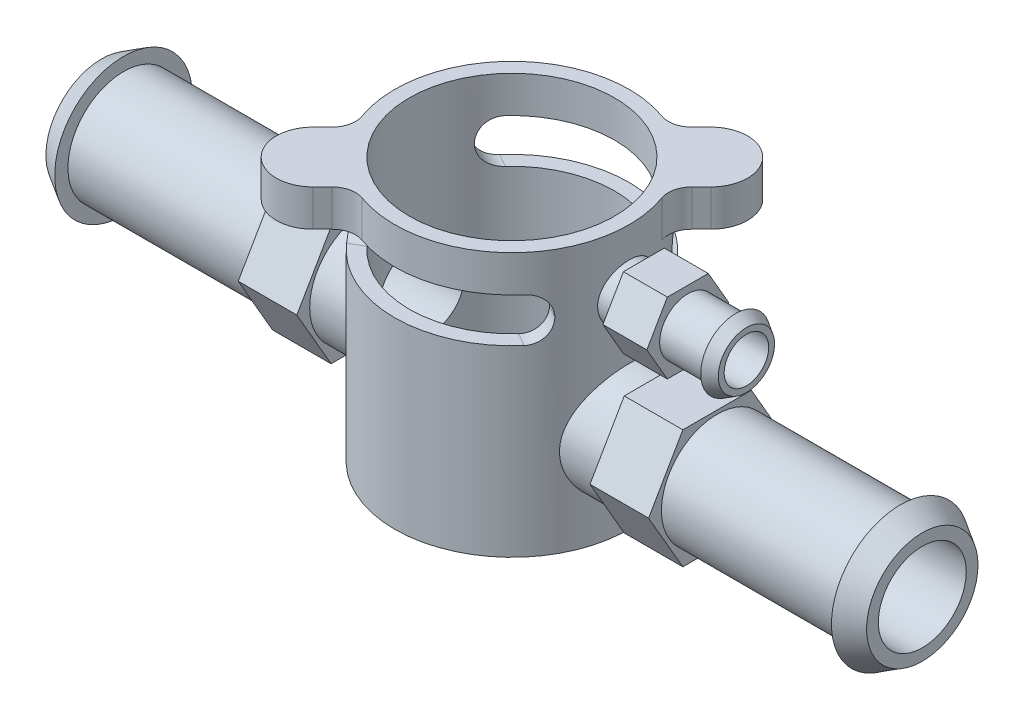
SolidWorks part; units mm, degrees
material "Chrome Stainless Steel"
ref_plane "Front Plane" through (0, 0, 0) normal (0, 0, 1) x (1, 0, 0)
ref_plane "Top Plane" through (0, 0, 0) normal (0, 1, 0) x (1, 0, 0)
ref_plane "Right Plane" through (0, 0, 0) normal (1, 0, 0) x (0, 0, -1)
ref_plane "Plane1" through (0, 0, 0) normal (-0.7071, 0, 0.7071) x (0.7071, 0, 0.7071)
sketch "Sketch1" plane through (0, 0, 0) normal (0, 1, 0) x (1, 0, 0)
  circle A0 centre (0, 0) radius 25.4
  dimension "D1" = 50.8
extrude "Boss-Extrude1" add sketch "Sketch1" along normal blind 57.15
sketch "Sketch2" plane through (0, 0, 0) normal (1, 0, 0) x (0, 0, -1)
  line L0 (0, 0) -> (0, 58.6228) construction
  line L2 (-7.424, 31.9088) -> (-14.848, 19.05)
  line L3 (-14.848, 19.05) -> (-7.424, 6.1912)
  line L4 (-7.424, 6.1912) -> (7.424, 6.1912)
  line L5 (7.424, 6.1912) -> (14.848, 19.05)
  line L6 (14.848, 19.05) -> (7.424, 31.9088)
  line L7 (7.424, 31.9088) -> (-7.424, 31.9088)
  line L8 (4.4361, 52.1335) -> (-4.4361, 52.1335)
  line L9 (-4.4361, 52.1335) -> (-8.8721, 44.45)
  line L10 (-8.8721, 44.45) -> (-4.4361, 36.7665)
  line L11 (-4.4361, 36.7665) -> (4.4361, 36.7665)
  line L12 (4.4361, 36.7665) -> (8.8721, 44.45)
  line L13 (8.8721, 44.45) -> (4.4361, 52.1335)
  circle A0 centre (0, 19.05) radius 9.525
  circle A1 centre (0, 44.45) radius 4.826
  circle A2 centre (0, 19.05) radius 12.065
  circle A3 centre (0, 44.45) radius 6.096
  circle A4 centre (0, 19.05) radius 12.8588 construction
  circle A5 centre (0, 44.45) radius 7.6835 construction
  dimension "D1" = 19.05
  dimension "D3" = 9.652
  dimension "D7" = 0.7937
  dimension "D8" = 1.5875
  dimension "D4" = 25.4
  dimension "D5" = 19.05
  dimension "D2" = 2.54
  dimension "D6" = 1.27
extrude "Boss-Extrude2" add sketch "Sketch2" along normal blind 88.9 contours A2
extrude "Boss-Extrude3" add sketch "Sketch2<3>" along normal blind 50.8 contours A3
sketch "Sketch2<3>" plane through (0, 0, 0) normal (1, 0, 0) x (0, 0, -1) same geometry as "Sketch2"
sketch "Sketch3" plane through (0, 0, 0) normal (0, 0, 1) x (1, 0, 0)
  line L0 (88.9, 31.115) -> (84.1375, 33.9725)
  line L1 (84.1375, 33.9725) -> (84.1375, 31.115)
  line L2 (88.9, 31.115) -> (25.4, 31.115) construction
  line L3 (84.1375, 31.115) -> (88.9, 31.115)
  dimension "D1" = 4.7625
  dimension "D2" = 2.8575
revolve "Revolve1" add sketch "Sketch3" angle 360 about axis through (88.9, 19.05, 0) along (-1, 0, 0)
sketch "Sketch4" plane through (0, 0, 0) normal (0, 0, 1) x (1, 0, 0)
  line L0 (50.8, 50.546) -> (48.4187, 50.546)
  line L1 (50.8, 50.546) -> (25.4, 50.546) construction
  line L2 (48.4187, 50.546) -> (48.4187, 51.9748)
  line L3 (48.4187, 51.9748) -> (50.8, 50.546)
  dimension "D1" = 2.3813
  dimension "D2" = 1.4287
revolve "Revolve2" add sketch "Sketch4" angle 360 about axis through (50.8, 44.45, 0) along (-1, 0, 0)
extrude "Boss-Extrude5" add sketch "Sketch2<13>" along normal blind 12.7 from offset 31.75 contours L7 L2 L3 L4 L5 L6
sketch "Sketch2<13>" plane through (0, 0, 0) normal (1, 0, 0) x (0, 0, -1) same geometry as "Sketch2"
extrude "Boss-Extrude6" add sketch "Sketch2<14>" along normal blind 9.525 from offset 28.575 contours L9 L10 L11 L12 L13 L8
sketch "Sketch2<14>" plane through (0, 0, 0) normal (1, 0, 0) x (0, 0, -1) same geometry as "Sketch2"
mirror "Mirror2" about plane through (0, 0, 0) normal (1, 0, 0) of "Revolve1", "Boss-Extrude5", "Boss-Extrude2"
sketch "Sketch8" plane through (0, 57.15, 0) normal (0, 1, 0) x (1, 0, 0)
  circle A0 centre (0, 0) radius 25.4 construction
  circle A1 centre (0, 0) radius 25.4 construction
  circle A2 centre (0, 0) radius 22.225
  dimension "D1" = 3.175
extrude "Cut-Extrude2" cut sketch "Sketch8" against normal offset from surface (53.975 mm away) 3.175 up to face at (0, 0, 25.4)
ref_plane "Plane2" through (0, 0, 0) normal (-0.5, 0, 0.866) x (0, -1, 0)
ref_plane "Plane3" through (0, 44.45, 0) normal (0, 1, 0) x (1, 0, 0)
sketch "Sketch7" plane through (0, 44.45, 0) normal (0, 1, 0) x (1, 0, 0)
  line L0 (19.2474, 11.1125) -> (21.997, 12.7)
  line L1 (0, 0) -> (25.4, 0) construction
  line L2 (19.2474, -11.1125) -> (21.997, -12.7)
  line L3 (-19.2474, -11.1125) -> (-21.997, -12.7)
  line L4 (-19.2474, 11.1125) -> (-21.997, 12.7)
  line L5 (0, 0) -> (19.2474, -11.1125) construction
  line L6 (0, 0) -> (-19.2474, -11.1125) construction
  line L7 (0, 0) -> (-19.2474, 11.1125) construction
  line L8 (0, 0) -> (19.2474, 11.1125) construction
  circle A0 centre (0, 0) radius 25.4 construction
  arc A1 (21.997, 12.7) -> (-21.997, 12.7) centre (0, 0) ccw
  arc A2 (21.997, -12.7) -> (25.4, 0) centre (0, 0) ccw construction
  arc A3 (25.4, 0) -> (21.997, 12.7) centre (0, 0) ccw construction
  arc A4 (-21.997, 12.7) -> (-21.997, -12.7) centre (0, 0) ccw construction
  arc A5 (-21.997, -12.7) -> (21.997, -12.7) centre (0, 0) ccw
  arc A7 (-19.2474, -11.1125) -> (19.2474, -11.1125) centre (0, 0) ccw
  arc A8 (-19.2474, 11.1125) -> (-19.2474, -11.1125) centre (0, 0) ccw construction
  arc A9 (19.2474, -11.1125) -> (22.225, 0) centre (0, 0) ccw construction
  arc A10 (19.2474, 11.1125) -> (-19.2474, 11.1125) centre (0, 0) ccw
  arc A11 (22.225, 0) -> (19.2474, 11.1125) centre (0, 0) ccw construction
  circle A12 centre (0, 0) radius 22.225 construction
  dimension "D2" = 22.225
  dimension "D1" = 30
extrude "Cut-Extrude1" cut sketch "Sketch7" against normal mid plane 9.525
fillet "Fillet2" radius 4.7625 8 edges at (20.6222, 49.2125, -11.9063) (20.6222, 39.6875, -11.9063) (-20.6222, 49.2125, -11.9063) (-20.6222, 39.6875, -11.9063) (-20.6222, 49.2125, 11.9063) (-20.6222, 39.6875, 11.9063) (20.6222, 49.2125, 11.9063) (20.6222, 39.6875, 11.9063)
sketch "Sketch5" plane through (0, 57.15, 0) normal (0, 1, 0) x (1, 0, 0)
  line L0 (-21.5526, -21.5526) -> (21.5526, 21.5526) construction
  line L2 (-35.5409, 0) -> (35.5409, 0) construction
  line L3 (11.4483, 22.6737) -> (15.94, 27.1653)
  line L4 (15.94, 27.1653) -> (27.1653, 15.94) construction
  line L5 (27.1653, 15.94) -> (22.6737, 11.4483)
  circle A0 centre (0, 0) radius 25.4 construction
  arc A1 (15.94, 27.1653) -> (27.1653, 15.94) centre (21.5526, 21.5526) cw
  arc A2 (22.6737, 11.4483) -> (11.4483, 22.6737) centre (0, 0) ccw
  point P0 (0, 0)
  point P6 (0, 0)
  dimension "D1" = 45
  dimension "D3" = 15.875
  dimension "D2" = 30.48
extrude "Boss-Extrude4" add sketch "Sketch5" against normal up to surface (7.9375 mm away) contours A1 L5 A2 L3 up to face at (0, 49.2125, -19.8008)
fillet "Fillet1" radius 5.08 2 edges at (11.4483, 53.1812, -22.6737) (22.6737, 53.1812, -11.4483)
mirror "Mirror1" about plane through (0, 0, 0) normal (-0.7071, 0, 0.7071) of "Fillet1", "Boss-Extrude4"
extrude "Cut-Extrude3" cut sketch "Sketch2<10>" against normal through all both and the other way through all contours A0
sketch "Sketch2<10>" plane through (0, 0, 0) normal (1, 0, 0) x (0, 0, -1) same geometry as "Sketch2"
extrude "Cut-Extrude5" cut sketch "Sketch2<12>" along normal through all contours A1
sketch "Sketch2<12>" plane through (0, 0, 0) normal (1, 0, 0) x (0, 0, -1) same geometry as "Sketch2"
equation "\"D19@Boss-Extrude2\"=2"
equation "\"D2@Sketch3\"=\"D1@Sketch3\"*3/5"
equation "\"D2@Sketch4\"=\"D1@Sketch4\"*3/5"
equation "\"D2@Sketch5\"=\"D1@Sketch1\"*3/5"
